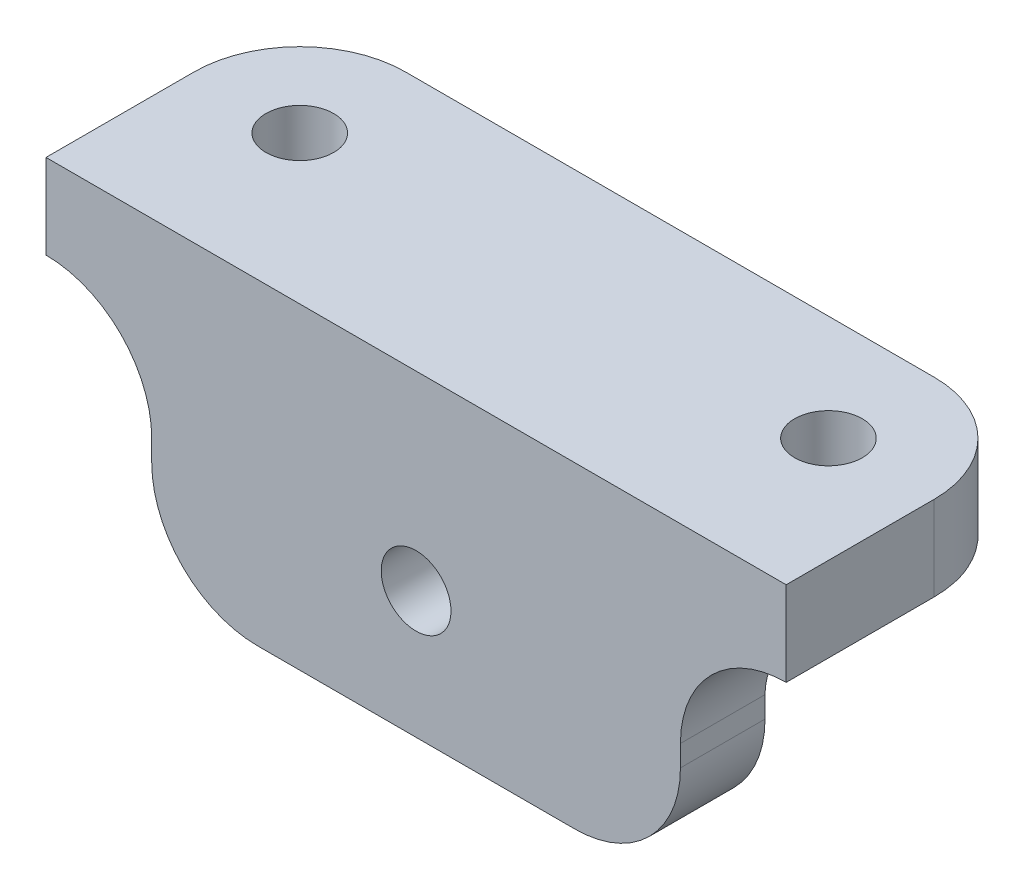
SolidWorks part; units mm, degrees
ref_plane "Alzado" through (0, 0, 0) normal (0, 0, 1) x (1, 0, 0)
ref_plane "Planta" through (0, 0, 0) normal (0, 1, 0) x (1, 0, 0)
ref_plane "Vista lateral" through (0, 0, 0) normal (1, 0, 0) x (0, 0, -1)
sketch "Croquis1" plane through (0, 0, 0) normal (0, 1, 0) x (1, 0, 0)
  line L1 (0, 0) -> (35, 0)
  line L2 (0, 0) -> (0, 12)
  line L3 (0, 12) -> (35, 12)
  line L4 (35, 0) -> (35, 12)
  circle A0 centre (5, 7) radius 1.6
  circle A1 centre (30, 7) radius 1.6
  dimension "D2" = 3.2
  dimension "D1" = 35
  dimension "D3" = 12
  dimension "D4" = 7
  dimension "D5" = 25
  dimension "D6" = 5
extrude "Saliente-Extruir1" add sketch "Croquis1" along normal blind 4
sketch "Croquis2" plane through (0, 0, 0) normal (0, -1, 0) x (1, 0, 0)
  line L0 (30, -7) -> (30, 0) construction
  line L1 (5, 0) -> (30, 0)
  line L2 (5, 0) -> (5, -4)
  line L3 (5, -4) -> (30, -4)
  line L4 (30, 0) -> (30, -4)
  line L5 (0, 0) -> (35, 0) construction
  line L6 (5, -7) -> (5, 0) construction
  dimension "D1" = 4
extrude "Saliente-Extruir2" add sketch "Croquis2" along normal blind 11
sketch "Croquis3" plane through (0, 0, 0) normal (0, -1, 0) x (1, 0, 0)
  line L1 (8.3486, -7) -> (6.6743, -4.1)
  line L2 (6.6743, -4.1) -> (3.3257, -4.1)
  line L3 (3.3257, -4.1) -> (1.6514, -7)
  line L4 (1.6514, -7) -> (3.3257, -9.9)
  line L5 (3.3257, -9.9) -> (6.6743, -9.9)
  line L6 (6.6743, -9.9) -> (8.3486, -7)
  line L7 (33.3486, -7) -> (31.6743, -4.1)
  line L8 (31.6743, -4.1) -> (28.3257, -4.1)
  line L9 (28.3257, -4.1) -> (26.6514, -7)
  line L10 (26.6514, -7) -> (28.3257, -9.9)
  line L11 (28.3257, -9.9) -> (31.6743, -9.9)
  line L12 (31.6743, -9.9) -> (33.3486, -7)
  circle A0 centre (5, -7) radius 2.9 construction
  circle A1 centre (30, -7) radius 2.9 construction
  dimension "D1" = 5.8
  dimension "D2" = 5.8
extrude "Cortar-Extruir1" cut sketch "Croquis3" against normal blind 1
sketch "Croquis4" plane through (0, 0, 0) normal (0, 0, 1) x (1, 0, 0)
  line L0 (17.5, -11) -> (17.5, 4) construction
  line L1 (30, -11) -> (5, -11) construction
  line L2 (0, 4) -> (35, 4) construction
  circle A0 centre (17.5, -5) radius 1.65
  dimension "D1" = 3.3
  dimension "D2" = 6
extrude "Cortar-Extruir2" cut sketch "Croquis4" against normal up to surface (4 mm away) up to face at (17.5, -5.5, -4)
sketch "Croquis5" plane through (0, 0, -4) normal (0, 0, -1) x (-1, 0, 0)
  line L1 (-20.8486, -5) -> (-19.1743, -7.9)
  line L2 (-19.1743, -7.9) -> (-15.8257, -7.9)
  line L3 (-15.8257, -7.9) -> (-14.1514, -5)
  line L4 (-14.1514, -5) -> (-15.8257, -2.1)
  line L5 (-15.8257, -2.1) -> (-19.1743, -2.1)
  line L6 (-19.1743, -2.1) -> (-20.8486, -5)
  circle A0 centre (-17.5, -5) radius 2.9 construction
  dimension "D1" = 5.8
extrude "Cortar-Extruir3" cut sketch "Croquis5" against normal blind 1
fillet "Redondeo1" radius 5 7 edges at (5, -11, -2) (30, -11, -2) (17.5, 0, -4) (30, 0, -2) (5, 0, -2) (0, 2, -12) (35, 2, -12)
